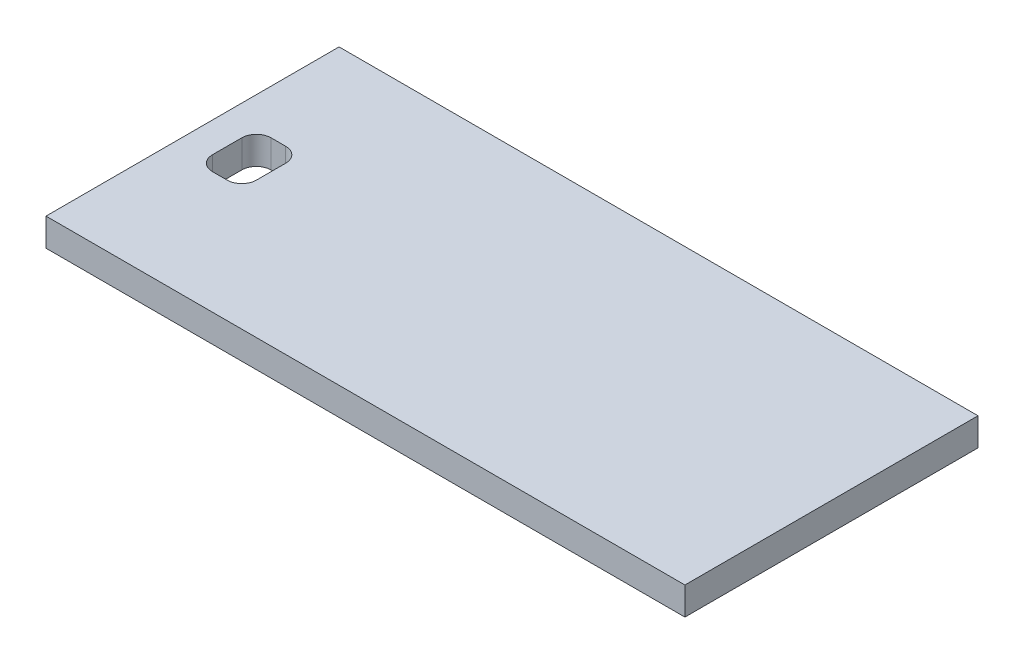
SolidWorks part; units mm, degrees
ref_plane "前视基准面" through (0, 0, 0) normal (0, 0, 1) x (1, 0, 0)
ref_plane "上视基准面" through (0, 0, 0) normal (0, 1, 0) x (1, 0, 0)
ref_plane "右视基准面" through (0, 0, 0) normal (1, 0, 0) x (0, 0, -1)
sketch "草图1" plane through (0, 0, 0) normal (0, 1, 0) x (1, 0, 0)
  line L1 (-109, 50) -> (109, 50)
  line L2 (-109, 50) -> (-109, -50)
  line L3 (-109, -50) -> (109, -50)
  line L4 (109, 50) -> (109, -50)
  line L5 (-109, 50) -> (109, -50) construction
  line L6 (-109, -50) -> (109, 50) construction
  point P0 (0, 0)
  dimension "D1" = 218
  dimension "D2" = 100
extrude "凸台-拉伸1" add sketch "草图1" along normal blind 9.5
sketch "草图2" plane through (0, 9.5, 0) normal (0, 1, 0) x (1, 0, 0)
  line L1 (-83.7348, -8.4712) -> (-98.7348, -8.4712)
  line L2 (-83.7348, -8.4712) -> (-83.7348, 11.5288)
  line L3 (-83.7348, 11.5288) -> (-98.7348, 11.5288)
  line L4 (-98.7348, -8.4712) -> (-98.7348, 11.5288)
  line L5 (-83.7348, -8.4712) -> (-98.7348, 11.5288) construction
  line L6 (-83.7348, 11.5288) -> (-98.7348, -8.4712) construction
  point P0 (-91.2348, 1.5288)
  dimension "D1" = 15
  dimension "D2" = 20
extrude "切除-拉伸1" cut sketch "草图2" against normal through all
fillet "圆角1" radius 5 4 edges at (-98.7348, 4.75, 8.4712) (-83.7348, 4.75, 8.4712) (-83.7348, 4.75, -11.5288) (-98.7348, 4.75, -11.5288)
